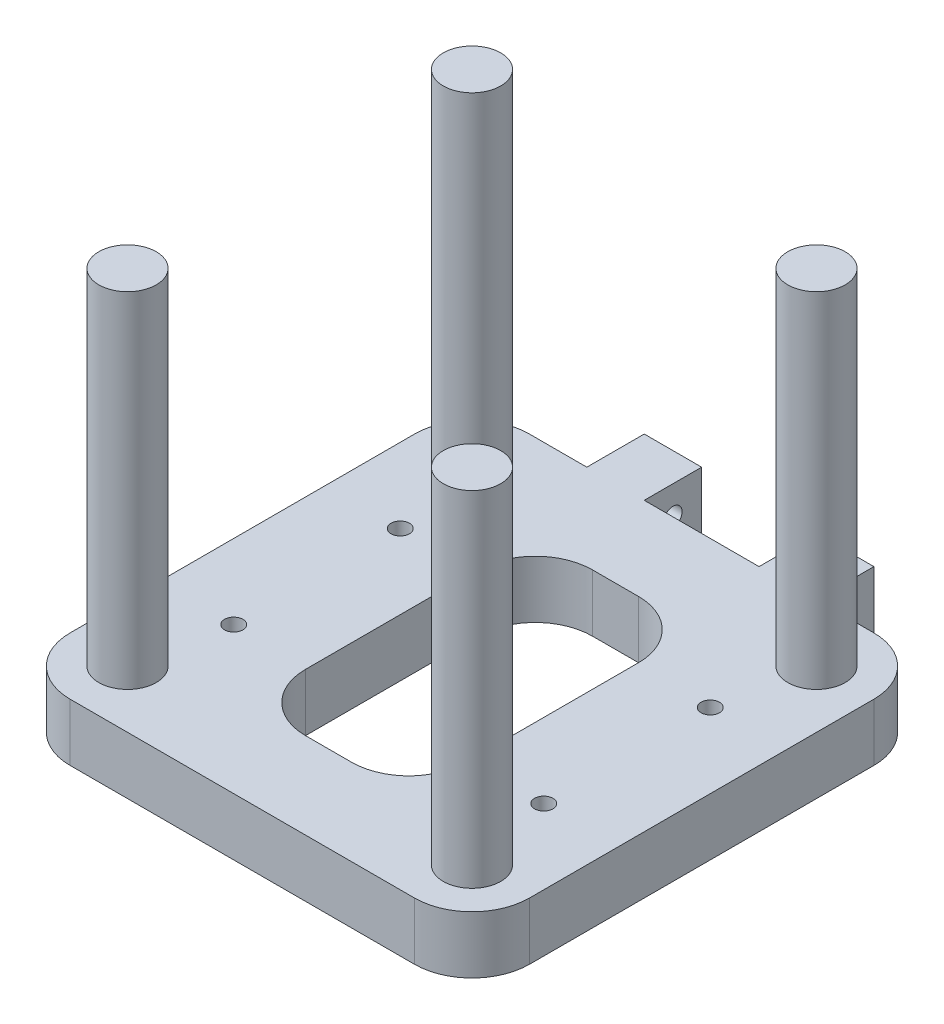
SolidWorks part; units mm, degrees
ref_plane "正面" through (0, 0, 0) normal (0, 0, 1) x (1, 0, 0)
ref_plane "平面" through (0, 0, 0) normal (0, 1, 0) x (1, 0, 0)
ref_plane "右側面" through (0, 0, 0) normal (1, 0, 0) x (0, 0, -1)
sketch "ｽｹｯﾁ1" plane through (0, 0, 0) normal (0, 1, 0) x (1, 0, 0)
  line L1 (-40, -40) -> (40, -40)
  line L2 (-40, -40) -> (-40, 40)
  line L3 (-40, 40) -> (40, 40)
  line L4 (40, -40) -> (40, 40)
  line L5 (-40, -40) -> (40, 40) construction
  line L6 (-40, 40) -> (40, -40) construction
  point P0 (0, 0)
  dimension "D1" = 80
extrude "ﾎﾞｽ - 押し出し1" add sketch "ｽｹｯﾁ1" along normal blind 10
fillet "ﾌｨﾚｯﾄ1" radius 10 4 edges at (-40, 5, -40) (40, 5, -40) (40, 5, 40) (-40, 5, 40)
sketch "ｽｹｯﾁ3" plane through (0, 10, 0) normal (0, 1, 0) x (1, 0, 0)
  line L0 (-40, 30) -> (-40, -30) construction
  line L1 (-4, -25) -> (4, -25)
  line L2 (-14, -15) -> (-14, 15)
  line L3 (-4, 25) -> (4, 25)
  line L4 (14, -15) -> (14, 15)
  line L5 (-14, -25) -> (14, 25) construction
  line L6 (-14, 25) -> (14, -25) construction
  arc A0 (4, -25) -> (14, -15) centre (4, -15) ccw
  arc A1 (-4, -25) -> (-14, -15) centre (-4, -15) cw
  arc A2 (4, 25) -> (14, 15) centre (4, 15) cw
  arc A3 (-14, 15) -> (-4, 25) centre (-4, 15) cw
  point P0 (0, 0)
  dimension "D1" = 26
  dimension "D3" = 10
  dimension "D2" = 50
extrude "ｶｯﾄ - 押し出し2" cut sketch "ｽｹｯﾁ3" against normal through all
sketch "ｽｹｯﾁ4" plane through (0, 10, 0) normal (0, 1, 0) x (1, 0, 0)
  circle A0 centre (-30, 30) radius 5
  circle A1 centre (30, 30) radius 5
  circle A2 centre (-30, -30) radius 5
  circle A3 centre (30, -30) radius 5
  arc A4 (-30, 40) -> (-40, 30) centre (-30, 30) ccw construction
  arc A5 (-40, -30) -> (-30, -40) centre (-30, -30) ccw construction
  arc A6 (30, -40) -> (40, -30) centre (30, -30) ccw construction
  arc A7 (40, 30) -> (30, 40) centre (30, 30) ccw construction
  dimension "D1" = 10
extrude "ﾎﾞｽ - 押し出し2" add sketch "ｽｹｯﾁ4" along normal blind 60
sketch "ｽｹｯﾁ5" plane through (0, 0, 0) normal (0, -1, 0) x (1, 0, 0)
  line L0 (40, 30) -> (40, -30) construction
  line L1 (-40, -30) -> (-40, 30) construction
  circle A0 centre (27, 14.5) radius 1.6
  circle A1 centre (-27, 14.5) radius 1.6
  circle A2 centre (-27, -14.5) radius 1.6
  circle A3 centre (27, -14.5) radius 1.6
  point P8 (-29.9303, 7.4141)
  point P9 (26.5388, 7.4141)
  point P12 (40, 0)
  point P15 (-40, 0)
  dimension "D3" = 3.2
  dimension "D4" = 13
  dimension "D5" = 13
  dimension "D1" = 14.5
  dimension "D2" = 14.5
  dimension "D6" = 13
  dimension "D7" = 13
  dimension "D8" = 14.5
  dimension "D9" = 14.5
extrude "ｶｯﾄ - 押し出し3" cut sketch "ｽｹｯﾁ5" against normal through all
sketch "ｽｹｯﾁ6" plane through (0, 0, -40) normal (0, 0, -1) x (-1, 0, 0)
  line L0 (-30, 10) -> (30, 10) construction
  line L1 (-20, 10) -> (-10, 10)
  line L2 (-20, 10) -> (-20, 0)
  line L3 (-20, 0) -> (-10, 0)
  line L4 (-10, 10) -> (-10, 0)
  line L5 (-20, 10) -> (-10, 0) construction
  line L6 (-20, 0) -> (-10, 10) construction
  line L7 (-30, 0) -> (30, 0) construction
  line L9 (10, 10) -> (20, 10)
  line L10 (10, 10) -> (10, 0)
  line L11 (10, 0) -> (20, 0)
  line L12 (20, 10) -> (20, 0)
  line L13 (10, 10) -> (20, 0) construction
  line L14 (10, 0) -> (20, 10) construction
  point P4 (-15, 5)
  point P13 (15, 5)
  dimension "D1" = 15
  dimension "D2" = 15
extrude "ﾎﾞｽ - 押し出し3" add sketch "ｽｹｯﾁ6" along normal blind 10
sketch "ｽｹｯﾁ7" plane through (0, 0, 0) normal (1, 0, 0) x (0, 0, -1)
  line L0 (50, 10) -> (40, 10) construction
  line L1 (50, 10) -> (50, 0) construction
  circle A0 centre (45, 5) radius 1.6
  point P4 (45, 10)
  point P7 (50, 5)
  dimension "D1" = 3.2
extrude "ｶｯﾄ - 押し出し4" cut sketch "ｽｹｯﾁ7" against normal through all both and the other way through all
